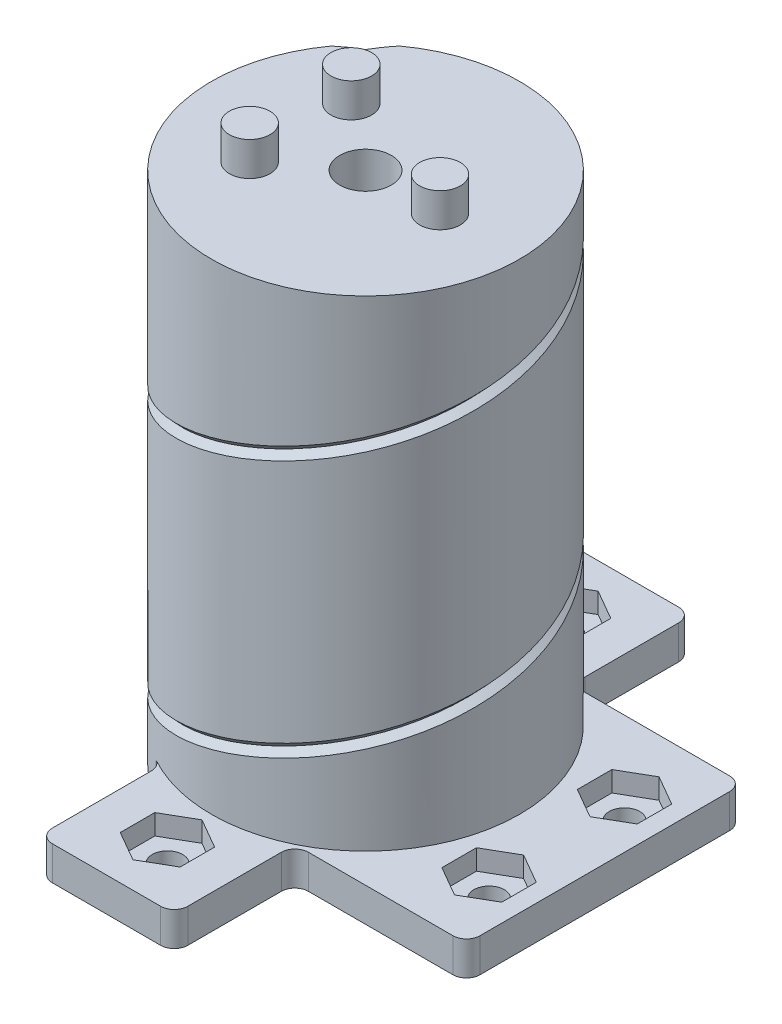
SolidWorks part; units mm, degrees
ref_plane "Front Plane" through (0, 0, 0) normal (0, 0, 1) x (1, 0, 0)
ref_plane "Top Plane" through (0, 0, 0) normal (0, 1, 0) x (1, 0, 0)
ref_plane "Right Plane" through (0, 0, 0) normal (1, 0, 0) x (0, 0, -1)
sketch "Sketch1" plane through (0, 0, 0) normal (0, 1, 0) x (1, 0, 0)
  line L0 (-22.75, 0) -> (22.75, 0) construction
  circle A0 centre (0, 0) radius 22.75
  dimension "D1" = 45.5
curve "Helix - Antenna Guide" pitch 38 height 152 radius 22.75 centre (0, 0, 0) axis (0, 1, 0) start towards (0, 0, 1)
extrude "Extrude - Main Body" add sketch "Sketch1<2>" along normal blind 76
sketch "Sketch1<2>" plane through (0, 0, 0) normal (0, 1, 0) x (1, 0, 0) same geometry as "Sketch1"
ref_point "Point2"
ref_plane "Plane1" through (-16.0867, 0, -16.0867) normal (-0.6834, 0.2569, 0.6834) x (-0.73, -0.2276, -0.6444)
sketch "Sketch15" plane through (-16.0867, 0, -16.0867) normal (-0.6834, 0.2569, 0.6834) x (-0.73, -0.2276, -0.6444)
  line L4 (0, 0) -> (0.2165, 0.8934)
  line L5 (0.2165, 0.8934) -> (-0.8934, 0.2165)
  line L8 (0, 0) -> (-0.2165, -0.8934)
  line L9 (-0.2165, -0.8934) -> (-0.8934, 0.2165)
  point P7 (-0.5549, -0.3384)
  dimension "D1" = 0.65
  dimension "D2" = 90
sweep "Cut - Antenna Wire Guide" cut profiles "Sketch15" path "Helix - Antenna Guide" align with end faces yes
sketch "Sketch26" plane through (0, 76, 0) normal (0, 1, 0) x (1, 0, 0)
  point P0 (0, 0)
hole_wizard ".3inch Hole" positions "Sketch27" profile "Sketch28" hole size "A" standard "ANSI Inch" end condition through all
sketch "Sketch27" plane through (0, 76, 0) normal (0, 1, 0) x (1, 0, 0)
  point P0 (0, 0)
sketch "Sketch28" plane through (0, 76, 0) normal (1, 0, 0) x (0, 0, 1)
  line L0 (0, 0) -> (0, 77.363)
  line L1 (0, 77.363) -> (3.81, 77.363)
  line L2 (3.81, 77.363) -> (3.81, 0)
  line L5 (3.81, 0) -> (0, 0)
  line L11 (0, -6.35) -> (0, 107.95) construction
  dimension "Thru Hole Dia." = 7.62
  dimension "Thru Hole Depth" = 77.363
sketch "Sketch29" plane through (0, 76, 0) normal (0, 1, 0) x (1, 0, 0)
  line L0 (11, 0) -> (-9.6061, 7.5) construction
  line L1 (-9.6061, 7.5) -> (-9.6061, -7.5) construction
  line L2 (-9.6061, -7.5) -> (11, 0) construction
  circle A0 centre (11, 0) radius 3
  circle A1 centre (-9.6061, 7.5) radius 3
  circle A2 centre (-9.6061, -7.5) radius 3
  dimension "D2" = 6
  dimension "D1" = 11
  dimension "D3" = 70
  dimension "D4" = 70
  dimension "D5" = 15
extrude "Extruded Peg" add sketch "Sketch29" along normal blind 5
sketch "Sketch42" plane through (0, 76, 0) normal (0, 1, 0) x (1, 0, 0)
  circle A1 centre (0, 0) radius 3.8105
  point P11 (3.8105, 0)
sketch "Sketch43" plane through (0, 0, 0) normal (0, -1, 0) x (1, 0, 0)
  line L0 (11, 0) -> (-9.6061, -7.5) construction
  line L1 (-9.6061, -7.5) -> (-9.6061, 7.5) construction
  line L2 (-9.6061, 7.5) -> (11, 0) construction
  circle A0 centre (11, 0) radius 3.125
  circle A1 centre (-9.6061, -7.5) radius 3.125
  circle A2 centre (-9.6061, 7.5) radius 3.125
  dimension "D2" = 6.25
  dimension "D1" = 11
  dimension "D3" = 70
  dimension "D4" = 70
  dimension "D5" = 15
extrude "PegCut" [suppressed] cut sketch "Sketch43" against normal blind 5.25
sketch "Sketch45" [suppressed] plane through (0, 0, 0) normal (0, -1, 0) x (1, 0, 0)
  circle A1 centre (0, 0) radius 3.8105
sketch "Sketch51" [suppressed] plane through (0, 76, 0) normal (0, 1, 0) x (1, 0, 0)
  line L0 (0, 0) -> (-22.75, 0) construction
  line L1 (0, 0) -> (22.75, 0) construction
  circle A0 centre (0, 0) radius 22.75 construction
ref_plane "LabelPlane" [suppressed] through (22.75, 76, 0) normal (1, 0, 0) x (0, 0, -1)
sketch "Sketch52" [suppressed] plane through (22.75, 76, 0) normal (1, 0, 0) x (0, 0, -1)
  line L0 (0, -76) -> (0, 0) construction
  text T0 "2" font "Century Gothic" height 10
  dimension "D1" = 4
  dimension "D2" = 40
sketch "Sketch53" [suppressed] plane through (0, 76, 0) normal (0, 1, 0) x (1, 0, 0)
  line L0 (0, 0) -> (-22.75, 0) construction
  line L1 (0, 0) -> (22.75, 0) construction
  arc A0 (-18.4043, 13.3732) -> (-13.3732, 18.4043) centre (0, 0) ccw construction
sketch "Sketch56" plane through (0, 0, 0) normal (0, -1, 0) x (1, 0, 0)
  line L0 (-22.75, 0) -> (22.75, 0) construction
  line L5 (-10, 38.25) -> (10, 38.25)
  line L6 (-10, 38.25) -> (-10, 10.25)
  line L15 (-10, 10.25) -> (10, 10.25)
  line L16 (10, 38.25) -> (10, 20.4343)
  line L19 (-10, -10.25) -> (10, -10.25)
  line L20 (10, -38.25) -> (10, -20.4343)
  line L21 (-10, -38.25) -> (10, -38.25)
  line L22 (-10, -38.25) -> (-10, -10.25)
  line L28 (10, 20.4343) -> (35.3394, 20.4343)
  line L29 (10, 10.25) -> (10, -10.25)
  line L30 (10, -20.4343) -> (35.3394, -20.4343)
  line L31 (35.3394, 20.4343) -> (35.3394, -20.4343)
  arc A1 (-13.3713, -18.4057) -> (-18.4057, -13.3713) centre (0, 0) ccw construction
  point P0 (0, 22.75)
  dimension "D1" = 20
  dimension "D2" = 28
extrude "BaseClamp" add sketch "Sketch56" against normal blind 5
fillet "Fillet1" radius 2 10 edges at (-10, 2.5, -38.25) (10, 2.5, -38.25) (-10, 2.5, 38.25) (10, 2.5, 38.25) (35.3394, 2.5, -20.4343) (35.3394, 2.5, 20.4343)
sketch "Sketch57" plane through (0, 5, 0) normal (0, 1, 0) x (1, 0, 0)
  line L0 (-8, 38.25) -> (8, 38.25) construction
  line L1 (-8, 38.25) -> (8, 38.25) construction
  line L2 (8, -38.25) -> (-8, -38.25) construction
  line L3 (10, 36.25) -> (10, 22.4343) construction
  line L4 (10, -22.4343) -> (10, -36.25) construction
  line L5 (0, 34.35) -> (-4.4167, 31.8)
  line L6 (28.2447, -4.9006) -> (23.828, -7.4506)
  line L7 (23.828, -7.4506) -> (23.828, -12.5506)
  line L8 (23.828, -12.5506) -> (28.2447, -15.1006)
  line L9 (28.2447, -15.1006) -> (32.6614, -12.5506)
  line L10 (32.6614, -12.5506) -> (32.6614, -7.4506)
  line L11 (32.6614, -7.4506) -> (28.2447, -4.9006)
  line L12 (28.2447, 15.1006) -> (23.828, 12.5506)
  line L13 (23.828, 12.5506) -> (23.828, 7.4506)
  line L14 (23.828, 7.4506) -> (28.2447, 4.9006)
  line L15 (28.2447, 4.9006) -> (32.6614, 7.4506)
  line L16 (32.6614, 7.4506) -> (32.6614, 12.5506)
  line L17 (32.6614, 12.5506) -> (28.2447, 15.1006)
  line L18 (-4.4167, 31.8) -> (-4.4167, 26.7)
  line L19 (-4.4167, 26.7) -> (0, 24.15)
  line L20 (0, 24.15) -> (4.4167, 26.7)
  line L21 (4.4167, 26.7) -> (4.4167, 31.8)
  line L22 (4.4167, 31.8) -> (0, 34.35)
  line L23 (0, -24.15) -> (-4.4167, -26.7)
  line L24 (-4.4167, -26.7) -> (-4.4167, -31.8)
  line L25 (-4.4167, -31.8) -> (0, -34.35)
  line L26 (0, -34.35) -> (4.4167, -31.8)
  line L27 (4.4167, -31.8) -> (4.4167, -26.7)
  line L28 (4.4167, -26.7) -> (0, -24.15)
  circle A0 centre (28.2447, -10.0006) radius 4.4167 construction
  circle A1 centre (28.2447, 10.0006) radius 4.4167 construction
  circle A2 centre (0, 29.25) radius 4.4167 construction
  circle A3 centre (0, -29.25) radius 4.4167 construction
  point P0 (0, 32.25)
  point P1 (0, -32.25)
  point P2 (28.2447, 10.0006)
  point P8 (28.2447, -10.0006)
  point P24 (0, 29.25)
  point P40 (0, -29.25)
  dimension "D1" = 6
  dimension "D2" = 6
  dimension "D3" = 28.2494
  dimension "D4" = 18.2447
  dimension "D5" = 18.2447
  dimension "D6" = 28.2494
  dimension "D7" = 5.1
  dimension "D8" = 5.1
hole_wizard "#8 Clearance Hole2" positions "Sketch58" profile "Sketch59" hole size "#8" standard "ANSI Inch" end condition through all
sketch "Sketch58" plane through (0, 5, 0) normal (0, 1, 0) x (1, 0, 0)
  line L0 (10, 36.25) -> (10, 22.4343) construction
  line L1 (-8, 38.25) -> (8, 38.25) construction
  line L2 (10, -22.4343) -> (10, -36.25) construction
  line L3 (8, -38.25) -> (-8, -38.25) construction
  point P0 (0, 29.25)
  point P3 (0, -29.25)
  point P6 (28.2447, -10.0006)
  point P8 (28.2447, 10.0006)
  dimension "D1" = 18.2447
  dimension "D2" = 28.2494
  dimension "D3" = 18.2447
  dimension "D4" = 28.2494
sketch "Sketch59" plane through (0, 5, -29.25) normal (1, 0, 0) x (0, 0, 1)
  line L0 (0, 0) -> (0, 6.363)
  line L1 (0, 6.363) -> (2.2479, 6.363)
  line L2 (2.2479, 6.363) -> (2.2479, 0)
  line L5 (2.2479, 0) -> (0, 0)
  line L11 (0, -6.35) -> (0, 107.95) construction
  dimension "Thru Hole Dia." = 4.4958
  dimension "Thru Hole Depth" = 6.363
ref_plane "Plane7" through (-22.75, 0, 0) normal (-1, 0, 0) x (0, 0, 1)
sketch "Sketch60" plane through (-22.75, 0, 0) normal (-1, 0, 0) x (0, 0, 1)
  line L0 (0, 0) -> (0, 76) construction
  line L1 (22.75, 76) -> (-22.75, 76) construction
  text T0 "1" font "Century Gothic" height 10
  dimension "D1" = 4
  dimension "D2" = 55
ref_plane "Plane8" [suppressed] through (22.75, 114, 0) normal (1, 0, 0) x (0, 0, -1)
sketch "Sketch62" [suppressed] plane through (22.75, 86.8571, 0) normal (1, 0, 0) x (0, 0, -1)
  line L0 (0, -86.8571) -> (0, 0) construction
  text T0 "3" font "Century Gothic" height 10
  dimension "D1" = 4
  dimension "D2" = 40
sketch "Sketch65" [suppressed] plane through (0, 0, 0) normal (0, -1, 0) x (1, 0, 0)
  circle A0 centre (0, 0) radius 19.75
  dimension "D1" = 39.5
extrude "Cut-Extrude1" [suppressed] cut sketch "Sketch62" against normal blind 3 draft 30
ref_plane "Plane9" [suppressed] through (0, 0, 0) normal (-0.7071, 0, 0.7071) x (0.7071, 0, 0.7071)
ref_plane "Plane10" [suppressed] through (22.75, 76, 0) normal (1, 0, 0) x (0, 0, -1)
sketch "Sketch66" [suppressed] plane through (22.75, 76, 0) normal (1, 0, 0) x (0, 0, -1)
  line L0 (0, 0) -> (0, -76) construction
  line L1 (22.75, 0) -> (-22.75, 0) construction
  text T0 "6" font "Century Gothic" height 10.5
  dimension "D1" = 45
  dimension "D2" = 4
extrude "NumberCut6" [suppressed] cut sketch "Sketch66" against normal blind 3 draft 30
sketch "Sketch70" plane through (0, 76, 0) normal (0, 1, 0) x (1, 0, 0)
  line L0 (-1.9053, -3.3) -> (1.9053, -3.3)
  line L1 (1.9053, -3.3) -> (3.8105, 0)
  line L2 (3.8105, 0) -> (1.9053, 3.3)
  line L3 (1.9053, 3.3) -> (-1.9053, 3.3)
  line L4 (-1.9053, 3.3) -> (-3.8105, 0)
  line L5 (-3.8105, 0) -> (-1.9053, -3.3)
  circle A0 centre (0, 0) radius 3.3 construction
extrude "Cut-Extrude3" cut sketch "Sketch70" against normal blind 26.8
sketch "Sketch72" [suppressed] plane through (0, 0, 0) normal (0, -1, 0) x (1, 0, 0)
  line L0 (-1.9053, -3.3) -> (1.9053, -3.3)
  line L1 (1.9053, -3.3) -> (3.8105, 0)
  line L2 (3.8105, 0) -> (1.9053, 3.3)
  line L3 (1.9053, 3.3) -> (-1.9053, 3.3)
  line L4 (-1.9053, 3.3) -> (-3.8105, 0)
  line L5 (-3.8105, 0) -> (-1.9053, -3.3)
  circle A0 centre (0, 0) radius 3.3 construction
  dimension "D1" = 6.6
extrude "Cut-Extrude4" [suppressed] cut sketch "Sketch72" against normal blind 24
sketch "Sketch74" [suppressed] plane through (0, 86.8571, 0) normal (0, 1, 0) x (1, 0, 0)
  circle A1 centre (0, 0) radius 3.8105
extrude "Cut-Extrude5" [suppressed] cut sketch "Sketch74" against normal blind 19.3
sketch "Sketch75" [suppressed] plane through (0, 0, 0) normal (0, -1, 0) x (1, 0, 0)
  circle A0 centre (0, 0) radius 3.8105
extrude "Cut-Extrude6" [suppressed] cut sketch "Sketch75" against normal blind 37.26
sketch "Sketch76" [suppressed] plane through (0, 86.8571, 0) normal (0, 1, 0) x (1, 0, 0)
  circle A0 centre (0, 0) radius 3.8105
extrude "Cut-Extrude7" [suppressed] cut sketch "Sketch76" against normal blind 19.64
sketch "Sketch77" [suppressed] plane through (0, 0, 0) normal (0, -1, 0) x (1, 0, 0)
  circle A0 centre (0, 0) radius 3.8105
extrude "Cut-Extrude8" [suppressed] cut sketch "Sketch77" against normal blind 31.16
sketch "Sketch78" [suppressed] plane through (22.75, 86.8571, 0) normal (1, 0, 0) x (0, 0, -1)
  line L0 (22.75, 0) -> (-22.75, 0) construction
  text T0 "5" font "Century Gothic" height 10
  dimension "D1" = 45
extrude "NumberCut5" [suppressed] cut sketch "Sketch78" against normal blind 3 draft 30
sketch "Sketch79" [suppressed] plane through (22.75, 86.8571, 0) normal (1, 0, 0) x (0, 0, -1)
  text T0 "4" font "Century Gothic" height 10
extrude "NumberCut4" [suppressed] cut sketch "Sketch79" against normal blind 3 draft 30
sketch "Sketch80" [suppressed] plane through (0, 76, 0) normal (0, 1, 0) x (1, 0, 0)
  circle A0 centre (0, 0) radius 3.8105
extrude "Cut-Extrude9" [suppressed] cut sketch "Sketch80" against normal blind 32.89
sketch "Sketch81" [suppressed] plane through (0, 0, 0) normal (0, -1, 0) x (1, 0, 0)
  circle A0 centre (0, 0) radius 3.8105
extrude "Cut-Extrude10" [suppressed] cut sketch "Sketch81" against normal blind 17.91
sketch "Sketch82" [suppressed] plane through (22.75, 76, 0) normal (1, 0, 0) x (0, 0, -1)
  line L0 (22.75, 0) -> (-22.75, 0) construction
  text T0 "7" font "Century Gothic" height 10.5
  dimension "D1" = 45
  dimension "D2" = 4
extrude "Cut-Extrude12" cut sketch "Sketch57" against normal blind 3
sketch "Sketch83" [suppressed] plane through (0, 76, 0) normal (0, 1, 0) x (1, 0, 0)
  circle A0 centre (0, 0) radius 2.15
extrude "Cut-Extrude13" [suppressed] cut sketch "Sketch83" against normal through all
equation "\"pegD\"=10"
equation "\"pegHoleD\"=0.5"
equation "\"pegHoleOffset\"=0.5"
